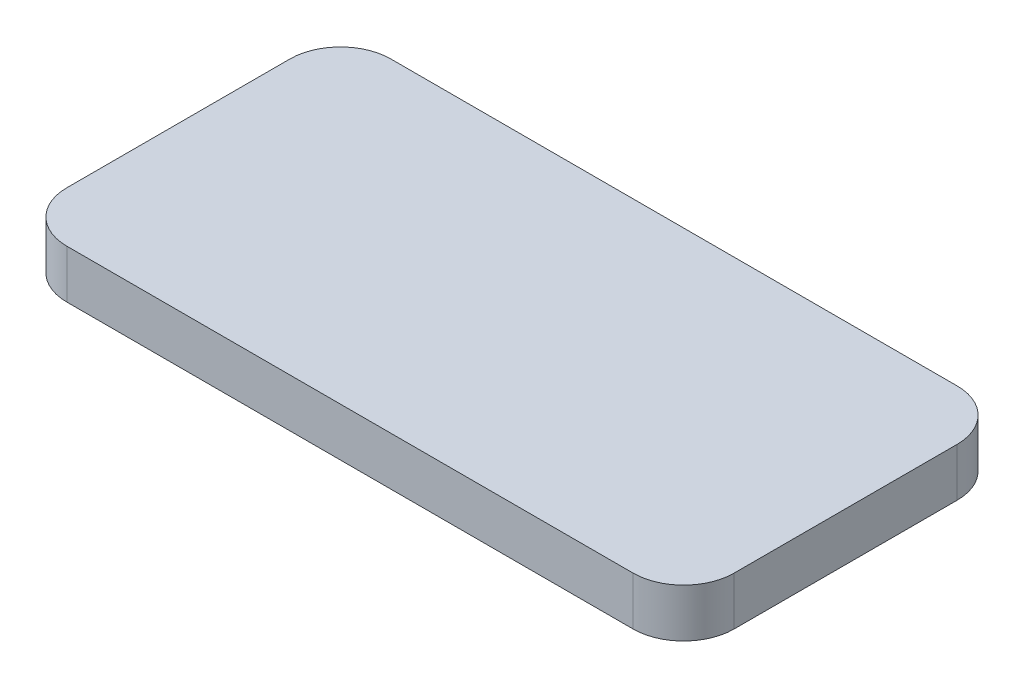
SolidWorks part; units mm, degrees
ref_plane "Front Plane" through (0, 0, 0) normal (0, 0, 1) x (1, 0, 0)
ref_plane "Top Plane" through (0, 0, 0) normal (0, 1, 0) x (1, 0, 0)
ref_plane "Right Plane" through (0, 0, 0) normal (1, 0, 0) x (0, 0, -1)
sketch "Sketch1" plane through (0, 0, 0) normal (0, 1, 0) x (1, 0, 0)
  line L1 (-14.849, -8.5001) -> (14.849, -8.5001)
  line L2 (-17.5006, -5.8485) -> (-17.5006, 5.8485)
  line L3 (-14.849, 8.5001) -> (14.849, 8.5001)
  line L4 (17.5006, -5.8485) -> (17.5006, 5.8485)
  line L5 (-17.5006, -8.5001) -> (17.5006, 8.5001) construction
  line L6 (-17.5006, 8.5001) -> (17.5006, -8.5001) construction
  arc A0 (-17.5006, 5.8485) -> (-14.849, 8.5001) centre (-14.849, 5.8485) cw
  arc A1 (-14.849, -8.5001) -> (-17.5006, -5.8485) centre (-14.849, -5.8485) cw
  arc A2 (14.849, -8.5001) -> (17.5006, -5.8485) centre (14.849, -5.8485) ccw
  arc A3 (14.849, 8.5001) -> (17.5006, 5.8485) centre (14.849, 5.8485) cw
  point P0 (0, 0)
  point P18 (0, 0)
  point P19 (-17.5006, 5.8485)
  dimension "D2" = 35.0012
  dimension "D3" = 17.0002
extrude "Boss-Extrude1" add sketch "Sketch1" along normal blind 2.54
